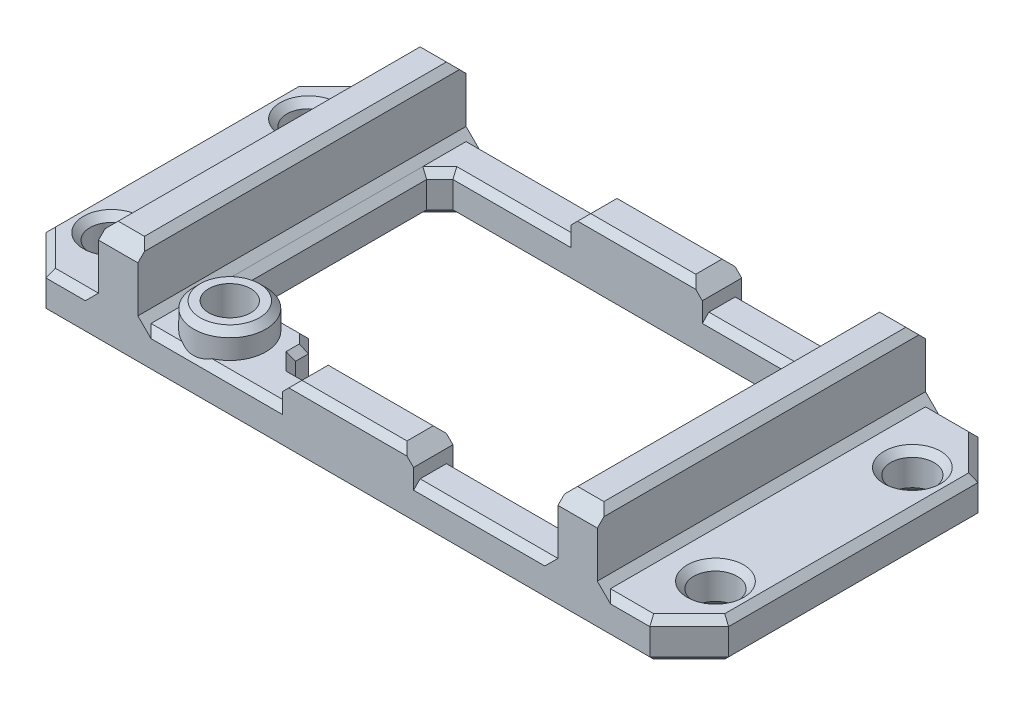
SolidWorks part; units mm, degrees
ref_plane "Front Plane" through (0, 0, 0) normal (0, 0, 1) x (1, 0, 0)
ref_plane "Top Plane" through (0, 0, 0) normal (0, 1, 0) x (1, 0, 0)
ref_plane "Right Plane" through (0, 0, 0) normal (1, 0, 0) x (0, 0, -1)
sketch "Sketch1" plane through (0, 0, 0) normal (0, 1, 0) x (1, 0, 0)
  line L0 (-17.5, -12.5) -> (17.5, 12.5) construction
  line L1 (-17.5, 12.5) -> (17.5, 12.5)
  line L2 (-17.5, 12.5) -> (-17.5, -12.5)
  line L3 (-17.5, -12.5) -> (17.5, -12.5)
  line L4 (17.5, 12.5) -> (17.5, -12.5)
  point P4 (0, 0)
  dimension "D1" = 35
  dimension "D2" = 25
extrude "Boss-Extrude1" add sketch "Sketch1" along normal blind 3
sketch "Sketch2" plane through (0, 3, 0) normal (0, 1, 0) x (1, 0, 0)
  line L0 (0, 12.5) -> (0, -12.5) construction
  line L1 (17.5, 12.5) -> (-17.5, 12.5) construction
  line L2 (-17.5, -12.5) -> (17.5, -12.5) construction
  line L3 (-17.5, 0) -> (17.5, 0) construction
  line L4 (-17.5, 12.5) -> (-17.5, -12.5) construction
  line L5 (17.5, -12.5) -> (17.5, 12.5) construction
  circle A0 centre (-12, -9.5) radius 1.6
  dimension "D3" = 3.2
  dimension "D1" = 12
  dimension "D2" = 3
extrude "Cut-Extrude1" cut sketch "Sketch2" against normal blind 3
sketch "Sketch3" plane through (0, 3, 0) normal (0, 1, 0) x (1, 0, 0)
  line L0 (0, 12.5) -> (0, -12.5) construction
  line L1 (17.5, 12.5) -> (-17.5, 12.5) construction
  line L2 (-17.5, -12.5) -> (17.5, -12.5) construction
  line L3 (17.5, -12.5) -> (26, -12.5)
  line L5 (-17.5, -12.5) -> (-26, -12.5)
  line L6 (-17.5, -12.5) -> (-17.5, 12.5)
  line L7 (-17.5, 12.5) -> (-26, 12.5)
  line L8 (-26, -12.5) -> (-26, 12.5)
  line L9 (17.5, -12.5) -> (17.5, 12.5)
  line L10 (17.5, 12.5) -> (26, 12.5)
  line L11 (26, -12.5) -> (26, 12.5)
  dimension "D1" = 26
  dimension "D2" = 25
extrude "Boss-Extrude2" add sketch "Sketch3" against normal blind 3
sketch "Sketch4" plane through (0, 3, 0) normal (0, 1, 0) x (1, 0, 0)
  line L0 (0, 0) -> (0, -12.5) construction
  line L1 (-26, -12.5) -> (26, -12.5) construction
  line L2 (0, 0) -> (-26, 0) construction
  line L3 (-26, 12.5) -> (-26, -12.5) construction
  line L4 (-23, 0) -> (-23, -12.5) construction
  line L5 (-23, 0) -> (-23, 7.5) construction
  circle A0 centre (-23, -7.5) radius 1.65
  circle A1 centre (-23, 7.5) radius 1.65
  circle A2 centre (23, -7.5) radius 1.65
  circle A3 centre (23, 7.5) radius 1.65
  dimension "D3" = 3.3
  dimension "D1" = 23
  dimension "D2" = 5
  dimension "D4" = 15
extrude "Cut-Extrude2" cut sketch "Sketch4" against normal blind 3
sketch "Sketch5" plane through (0, 3, 0) normal (0, 1, 0) x (1, 0, 0)
  line L0 (0, 12.5) -> (0, -12.5) construction
  line L1 (26, 12.5) -> (-26, 12.5) construction
  line L2 (-26, -12.5) -> (26, -12.5) construction
  line L3 (0, 0) -> (-26, 0) construction
  line L4 (-26, 12.5) -> (-26, -12.5) construction
  line L5 (-15, 12.5) -> (-15, -12.5) construction
  line L6 (0, 9.5) -> (-15, 9.5)
  line L7 (-15, 9.5) -> (-15, 0)
  line L8 (-15, 0) -> (-15, -6.5)
  line L9 (-15, -6.5) -> (-8, -6.5)
  line L10 (-8, -6.5) -> (-8, -9.5)
  line L11 (-8, -9.5) -> (0, -9.5)
  line L12 (0, -9.5) -> (15, -9.5)
  line L13 (15, -9.5) -> (15, 9.5)
  line L14 (15, 9.5) -> (0, 9.5)
  dimension "D1" = 15
  dimension "D2" = 3
  dimension "D3" = 3
  dimension "D4" = 3
  dimension "D5" = 8
extrude "Cut-Extrude3" cut sketch "Sketch5" against normal blind 3
sketch "Sketch6" plane through (0, 3, 0) normal (0, 1, 0) x (1, 0, 0)
  line L0 (0, -12.5) -> (0, 12.5) construction
  line L1 (-26, -12.5) -> (26, -12.5) construction
  line L2 (26, 12.5) -> (-26, 12.5) construction
  line L3 (16, -12.5) -> (19, -12.5)
  line L4 (-16, 12.5) -> (-19, 12.5)
  line L5 (-16, 12.5) -> (-16, -12.5)
  line L6 (-16, -12.5) -> (-19, -12.5)
  line L7 (-19, 12.5) -> (-19, -12.5)
  line L8 (16, 12.5) -> (16, -12.5)
  line L9 (16, 12.5) -> (19, 12.5)
  line L10 (19, 12.5) -> (19, -12.5)
  dimension "D1" = 16
  dimension "D2" = 3
extrude "Boss-Extrude3" add sketch "Sketch6" along normal blind 5
sketch "Sketch7" plane through (0, 3, 0) normal (0, 1, 0) x (1, 0, 0)
  line L0 (0, 12.5) -> (0, -12.5) construction
  line L1 (16, 12.5) -> (-16, 12.5) construction
  line L2 (-16, -12.5) -> (16, -12.5) construction
  line L3 (0, 12.5) -> (5, 12.5)
  line L4 (5, 12.5) -> (5, 9.5)
  line L5 (15, 9.5) -> (-15, 9.5) construction
  line L6 (5, 9.5) -> (-5, 9.5)
  line L7 (-5, 9.5) -> (-5, 12.5)
  line L8 (-5, 12.5) -> (0, 12.5)
  line L9 (0, -12.5) -> (-5, -12.5)
  line L10 (-5, -12.5) -> (-5, -9.5)
  line L11 (-8, -9.5) -> (15, -9.5) construction
  line L12 (-5, -9.5) -> (5, -9.5)
  line L13 (5, -9.5) -> (5, -12.5)
  line L14 (5, -12.5) -> (0, -12.5)
  circle A0 centre (-12, -9.5) radius 2.75
  circle A1 centre (-12, -9.5) radius 1.6
  dimension "D1" = 3.2
  dimension "D2" = 5.5
  dimension "D3" = 5
extrude "Boss-Extrude4" add sketch "Sketch7" along normal blind 2
chamfer "Chamfer1" distance 3 angle 45 4 edges at (26, 1.5, -12.5) (26, 1.5, 12.5) (-26, 1.5, -12.5) (-26, 1.5, 12.5)
chamfer "Chamfer2" distance 1 angle 45 8 edges at (17.5, 8, 12.5) (-17.5, 8, 12.5) (17.5, 8, -12.5) (-17.5, 8, -12.5) (5, 5, 11) (-5, 5, 11) (5, 5, -11) (-5, 5, -11)
chamfer "Chamfer3" distance 0.5 angle 45 4 edges at (19, 3, 0) (16, 3, 0) (-16, 3, 0) (-19, 3, 0)
chamfer "Chamfer4" distance 1 angle 45 6 edges at (-8, 1.5, 9.5) (-8, 1.5, 6.5) (-15, 1.5, 6.5) (15, 1.5, 9.5) (15, 1.5, -9.5) (-15, 1.5, -9.5)
chamfer "Chamfer5" distance 0.5 angle 45 25 edges at (-24.5, 0, -11) (-24.5, 0, 11) (0, 0, 12.5) (24.5, 0, 11) (24.5, 0, -11) (0, 0, -12.5) (-12, 0, 11.1) (-23, 0, 9.15) (23, 0, -9.15) (23, 0, 5.85) (-23, 0, -5.85) (-14.5, 0, 6) (-15, 0, -1.5) (-14.5, 0, -9) (0, 0, -9.5) (14.5, 0, -9) (15, 0, 0) (14.5, 0, 9) (3.5, 0, 9.5) (-7.5, 0, 9) (-8, 0, 8) (-8.5, 0, 7) (-11.5, 0, 6.5) (-26, 0, 0) (26, 0, 0)
chamfer "Chamfer6" distance 0.5 angle 45 32 edges at (-15, 3, -1.5) (-14.5, 3, 6) (-11.5, 3, 6.5) (-8.5, 3, 7) (-8, 3, 8) (-7.5, 3, 9) (-6, 3, 9.5) (9.5, 3, 9.5) (14.5, 3, 9) (15, 3, 0) (14.5, 3, -9) (9.5, 3, -9.5) (-9.5, 3, -9.5) (-14.5, 3, -9) (10.25, 3, 12.5) (-10.25, 3, 12.5) (-10.25, 3, -12.5) (10.25, 3, -12.5) (23, 3, 5.85) (23, 3, -9.15) (-23, 3, -5.85) (-23, 3, 9.15) (21.25, 3, 12.5) (24.5, 3, 11) (26, 3, 0) (24.5, 3, -11) (21.25, 3, -12.5) (-21.25, 3, 12.5) (-24.5, 3, 11) (-26, 3, 0) (-24.5, 3, -11) (-21.25, 3, -12.5)
chamfer "Chamfer7" distance 0.5 angle 45 8 edges at (19, 8, 0) (16, 8, 0) (-16, 8, 0) (-19, 8, 0) (0, 5, 12.5) (0, 5, 9.5) (0, 5, -12.5) (0, 5, -9.5)
chamfer "Chamfer8" distance 0.5 angle 45 1 edges at (-12, 5, 12.25)
